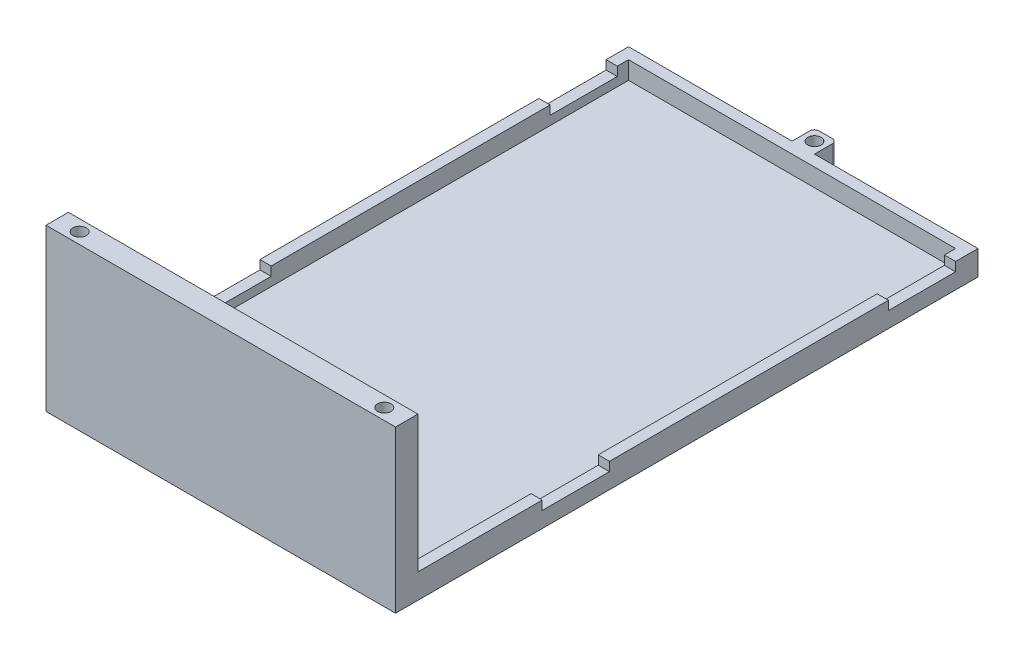
SolidWorks part; units mm, degrees
ref_plane "Front Plane" through (0, 0, 0) normal (0, 0, 1) x (1, 0, 0)
ref_plane "Top Plane" through (0, 0, 0) normal (0, 1, 0) x (1, 0, 0)
ref_plane "Right Plane" through (0, 0, 0) normal (1, 0, 0) x (0, 0, -1)
sketch "Sketch1" plane through (0, 0, 0) normal (0, 1, 0) x (1, 0, 0)
  line L1 (-78, -130) -> (78, -130)
  line L2 (-78, -130) -> (-78, 130)
  line L3 (-78, 130) -> (78, 130)
  line L4 (78, -130) -> (78, 130)
  line L5 (-78, -130) -> (78, 130) construction
  line L6 (-78, 130) -> (78, -130) construction
  point P0 (0, 0)
  dimension "D1" = 260
  dimension "D2" = 156
extrude "Boss-Extrude1" add sketch "Sketch1" along normal blind 3
sketch "Sketch2" plane through (0, 3, 0) normal (0, 1, 0) x (1, 0, 0)
  line L0 (78, -130) -> (78, 130) construction
  line L1 (-73, -120) -> (73, -120) construction
  line L2 (-73, -120) -> (-73, 125)
  line L3 (-73, 125) -> (73, 125)
  line L4 (73, -120) -> (73, 125)
  line L5 (-73, -120) -> (-78, -120)
  line L6 (73, -120) -> (78, -120)
  line L7 (-78, -130) -> (78, -130) construction
  line L8 (-78, 130) -> (-78, -130) construction
  line L9 (78, 130) -> (-78, 130) construction
  line L10 (78, -120) -> (78, 130)
  line L12 (-78, 130) -> (-78, -120)
  line L13 (78, 130) -> (-78, 130)
  point P0 (0, 0)
  dimension "D1" = 5
  dimension "D2" = 5
  dimension "D3" = 10
  dimension "D4" = 5
extrude "Boss-Extrude2" add sketch "Sketch2" along normal blind 8
sketch "Sketch3" plane through (0, 3, 0) normal (0, 1, 0) x (1, 0, 0)
  line L1 (-78, -130) -> (78, -130)
  line L2 (-78, -130) -> (-78, -120)
  line L3 (-78, -120) -> (78, -120)
  line L4 (78, -130) -> (78, -120)
  dimension "D1" = 10
extrude "Boss-Extrude3" add sketch "Sketch3" along normal blind 69
sketch "Sketch4" plane through (0, 72, 0) normal (0, 1, 0) x (1, 0, 0)
  line L0 (-78, -120) -> (-78, -130) construction
  line L1 (0, -120) -> (0, -130) construction
  line L2 (73, -120) -> (-73, -120) construction
  line L3 (-78, -130) -> (78, -130) construction
  circle A0 centre (-68, -125) radius 3
  circle A1 centre (68, -125) radius 3
  dimension "D1" = 6
  dimension "D2" = 10
  dimension "D3" = 5
extrude "Cut-Extrude1" cut sketch "Sketch4" against normal blind 10
sketch "Sketch5" plane through (0, 11, 0) normal (0, 1, 0) x (1, 0, 0)
  line L0 (-78, 105) -> (-73, 105) construction
  line L1 (-78, 130) -> (-78, -120) construction
  line L2 (-73, -120) -> (-73, 125) construction
  line L3 (-78, -49.5) -> (-73, -49.5) construction
  line L4 (-73, -120) -> (-73, 125) construction
  line L5 (-73, 125) -> (73, 125) construction
  line L7 (0, 125) -> (0, -120) construction
  line L8 (-78, 90) -> (-73, 90)
  line L9 (-78, 90) -> (-78, 120)
  line L10 (-78, 120) -> (-73, 120)
  line L11 (-73, 90) -> (-73, 120)
  line L12 (-78, 90) -> (-73, 120) construction
  line L13 (-78, 120) -> (-73, 90) construction
  line L14 (-78, -64.5) -> (-73, -64.5)
  line L15 (-78, -64.5) -> (-78, -34.5)
  line L16 (-78, -34.5) -> (-73, -34.5)
  line L17 (-73, -64.5) -> (-73, -34.5)
  line L18 (-78, -64.5) -> (-73, -34.5) construction
  line L19 (-78, -34.5) -> (-73, -64.5) construction
  line L20 (-73, 125) -> (73, 125) construction
  line L21 (73, -120) -> (-73, -120) construction
  line L22 (78, 120) -> (73, 120)
  line L23 (73, 90) -> (73, 120)
  line L24 (78, 90) -> (73, 90)
  line L25 (78, 90) -> (78, 120)
  line L26 (78, -34.5) -> (73, -34.5)
  line L27 (73, -64.5) -> (73, -34.5)
  line L28 (78, -64.5) -> (73, -64.5)
  line L29 (78, -64.5) -> (78, -34.5)
  point P14 (-75.5, 105)
  point P19 (-75.5, -49.5)
  dimension "D1" = 20
  dimension "D2" = 154.5
  dimension "D3" = 30
  dimension "D4" = 30
extrude "Cut-Extrude2" cut sketch "Sketch5" against normal blind 4
sketch "Sketch6" plane through (0, 11, 0) normal (0, 1, 0) x (1, 0, 0)
  line L0 (78, 130) -> (-78, 130) construction
  line L1 (-5, 140) -> (5, 140)
  line L2 (-5, 140) -> (-5, 130)
  line L3 (-5, 130) -> (5, 130)
  line L4 (5, 140) -> (5, 130)
  line L5 (-5, 140) -> (5, 130) construction
  line L6 (-5, 130) -> (5, 140) construction
  line L7 (-78, 130) -> (-78, 120) construction
  point P0 (0, 135)
  dimension "D1" = 10
  dimension "D2" = 10
  dimension "D3" = 78
extrude "Boss-Extrude4" add sketch "Sketch6" against normal blind 10
sketch "Sketch7" plane through (0, 11, 0) normal (0, 1, 0) x (1, 0, 0)
  line L0 (5, 140) -> (-5, 140) construction
  line L1 (-5, 140) -> (-5, 130) construction
  circle A0 centre (0, 135) radius 3
  dimension "D1" = 6
  dimension "D2" = 5
  dimension "D3" = 5
extrude "Cut-Extrude3" cut sketch "Sketch7" against normal blind 10
fillet "Fillet1" radius 2 2 edges at (-5, 6, -140) (5, 6, -140)
equation "\"t_wall\"= 5mm"
